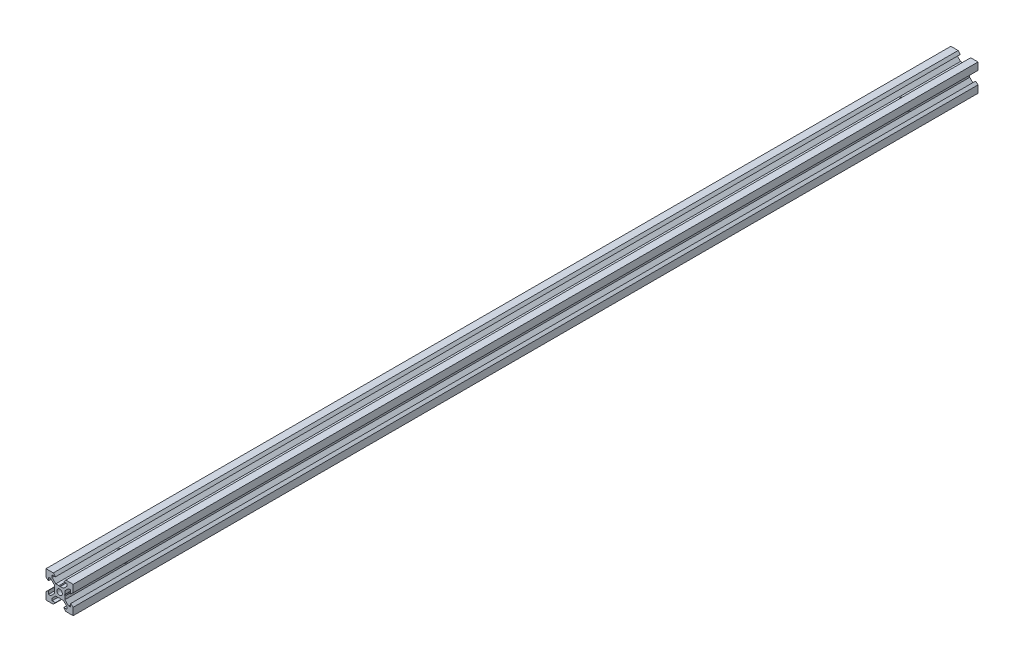
SolidWorks part; units mm, degrees
material "3.3535 (EN-AW 5754)"
ref_plane "Front Plane" through (0, 0, 0) normal (0, 0, 1) x (1, 0, 0)
ref_plane "Top Plane" through (0, 0, 0) normal (0, 1, 0) x (1, 0, 0)
ref_plane "Right Plane" through (0, 0, 0) normal (1, 0, 0) x (0, 0, -1)
sketch "Sketch1" plane through (0, 0, 0) normal (0, 0, 1) x (1, 0, 0)
  line L0 (10, 10) -> (4.6104, 10) construction
  line L1 (10, 10) -> (10, 4.6104) construction
  line L2 (10, -10) -> (10, -4.6104) construction
  line L3 (10, -10) -> (4.6104, -10) construction
  line L4 (10, 10) -> (10, 4.6104)
  line L5 (6.5607, 5.5) -> (8.2, 5.5)
  line L6 (5.5, 8.2) -> (5.5, 6.5607)
  line L7 (10, 10) -> (4.6104, 10)
  line L8 (10, 10) -> (10, 4.6104)
  line L9 (6.5607, 5.5) -> (3.9, 2.8393)
  line L10 (5.5, 6.5607) -> (2.8393, 3.9)
  line L11 (10, 4.6104) -> (8.2, 3.1)
  line L12 (4.6104, 10) -> (3.1, 8.2)
  line L13 (8.2, 3.1) -> (8.2, 5.5)
  line L14 (3.1, 8.2) -> (5.5, 8.2)
  line L15 (-6.5607, 5.5) -> (-8.2, 5.5)
  line L16 (6.5607, -5.5) -> (8.2, -5.5)
  line L17 (3.1, -8.2) -> (5.5, -8.2)
  line L18 (8.2, -3.1) -> (8.2, -5.5)
  line L19 (4.6104, -10) -> (3.1, -8.2)
  line L20 (10, -4.6104) -> (8.2, -3.1)
  line L21 (0.5196, -3.9) -> (0, -3.6)
  line L22 (0.5196, 3.9) -> (0, 3.6)
  line L23 (3.6, 0) -> (3.9, -0.5196)
  line L24 (3.9, 0.5196) -> (3.6, 0)
  line L25 (3.9, 0.5196) -> (3.9, 2.8393)
  line L26 (2.8393, 3.9) -> (0.5196, 3.9)
  line L27 (3.9, -2.8393) -> (3.9, -0.5196)
  line L28 (2.8393, -3.9) -> (0.5196, -3.9)
  line L29 (5.5, -6.5607) -> (2.8393, -3.9)
  line L30 (6.5607, -5.5) -> (3.9, -2.8393)
  line L31 (10, -10) -> (10, -4.6104)
  line L32 (10, -10) -> (4.6104, -10)
  line L33 (5.5, -8.2) -> (5.5, -6.5607)
  line L34 (-6.5607, -5.5) -> (-8.2, -5.5)
  line L35 (10, -10) -> (10, -4.6104)
  line L36 (0, 0) -> (0, 8.2) construction
  line L37 (-10, -10) -> (-4.6104, -10) construction
  line L38 (-10, -10) -> (-10, -4.6104) construction
  line L39 (-10, 10) -> (-10, 4.6104) construction
  line L40 (-10, 10) -> (-4.6104, 10) construction
  line L41 (-10, -10) -> (-10, -4.6104)
  line L43 (-5.5, -8.2) -> (-5.5, -6.5607)
  line L44 (-10, -10) -> (-4.6104, -10)
  line L45 (-10, -10) -> (-10, -4.6104)
  line L46 (-6.5607, -5.5) -> (-3.9, -2.8393)
  line L47 (-5.5, -6.5607) -> (-2.8393, -3.9)
  line L48 (-2.8393, -3.9) -> (-0.5196, -3.9)
  line L49 (-3.9, -2.8393) -> (-3.9, -0.5196)
  line L50 (-2.8393, 3.9) -> (-0.5196, 3.9)
  line L51 (-3.9, 0.5196) -> (-3.9, 2.8393)
  line L52 (-3.9, 0.5196) -> (-3.6, 0)
  line L53 (-3.6, 0) -> (-3.9, -0.5196)
  line L54 (-0.5196, 3.9) -> (0, 3.6)
  line L55 (-0.5196, -3.9) -> (0, -3.6)
  line L56 (-10, -4.6104) -> (-8.2, -3.1)
  line L57 (-4.6104, -10) -> (-3.1, -8.2)
  line L58 (-8.2, -3.1) -> (-8.2, -5.5)
  line L59 (-3.1, -8.2) -> (-5.5, -8.2)
  line L60 (-10, -10) -> (10, -10) construction
  line L61 (-10, -10) -> (-10, 10) construction
  line L62 (-3.1, 8.2) -> (-5.5, 8.2)
  line L63 (-8.2, 3.1) -> (-8.2, 5.5)
  line L64 (-4.6104, 10) -> (-3.1, 8.2)
  line L65 (-10, 4.6104) -> (-8.2, 3.1)
  line L66 (-5.5, 6.5607) -> (-2.8393, 3.9)
  line L67 (-6.5607, 5.5) -> (-3.9, 2.8393)
  line L68 (-10, 10) -> (-10, 4.6104)
  line L69 (-10, 10) -> (-4.6104, 10)
  line L70 (-5.5, 8.2) -> (-5.5, 6.5607)
  line L71 (-10, 10) -> (10, 10) construction
  line L72 (-10, 10) -> (-10, 4.6104)
  line L73 (10, -10) -> (10, 10) construction
  line L74 (-10, -10) -> (10, 10) construction
  line L75 (-10, 10) -> (10, -10) construction
  circle A0 centre (0, 0) radius 2
  dimension "D7" = 4
  dimension "D1" = 20
  dimension "D2" = 5.3896
  dimension "D3" = 4.5
  dimension "D4" = 50
  dimension "D5" = 1.8
  dimension "D6" = 1.5104
  dimension "D8" = 5.5
  dimension "D9" = 120
  dimension "D10" = 0.3
  dimension "D11" = 2.3197
  dimension "D12" = 7.8
  dimension "D13" = 7.8
  dimension "D14" = 1.5
  dimension "D15" = 2.6607
extrude "Boss-Extrude1" add sketch "Sketch1" along normal blind 666 contours L70 L62 L64 L69 L68 L65 L63 L15 L67 L51 L52 L53 L49 L46 L34 L58 L56 L41 L44 L57 L59 L43 L47 L48 L55 L21 L28 L29 L33 L17 L19 L32 L31 L20 L18 L16 L30 L27 L23 L24 L25 L9 L5 L13 L11 L4 L7 L12 L14 L6 L10 region at (9.7172, 7.3052, 0)
sketch "Sketch2" plane through (0, -3.9, 0) normal (0, -1, 0) x (-1, 0, 0)
  line L0 (0, -666) -> (0, -621) construction
  line L1 (0, -666) -> (0, 0) construction
  line L2 (0, 0) -> (0, -45) construction
  circle A0 centre (0, -621) radius 2
  circle A1 centre (0, -45) radius 2
  dimension "D2" = 4
  dimension "D4" = 4
  dimension "D1" = 45
  dimension "D3" = 45
extrude "Cut-Extrude1" cut sketch "Sketch2" against normal through all both and the other way through all
sketch "Sketch3" plane through (3.9, 0, 0) normal (1, 0, 0) x (0, 0, -1)
  line L0 (0, 0) -> (-45, 0) construction
  line L1 (-666, 0) -> (0, 0) construction
  line L2 (-666, 0) -> (-621, 0) construction
  circle A0 centre (-45, 0) radius 2
  circle A1 centre (-621, 0) radius 2
  dimension "D2" = 4
  dimension "D4" = 4
  dimension "D1" = 45
  dimension "D3" = 45
extrude "Cut-Extrude2" cut sketch "Sketch3" against normal through all both
